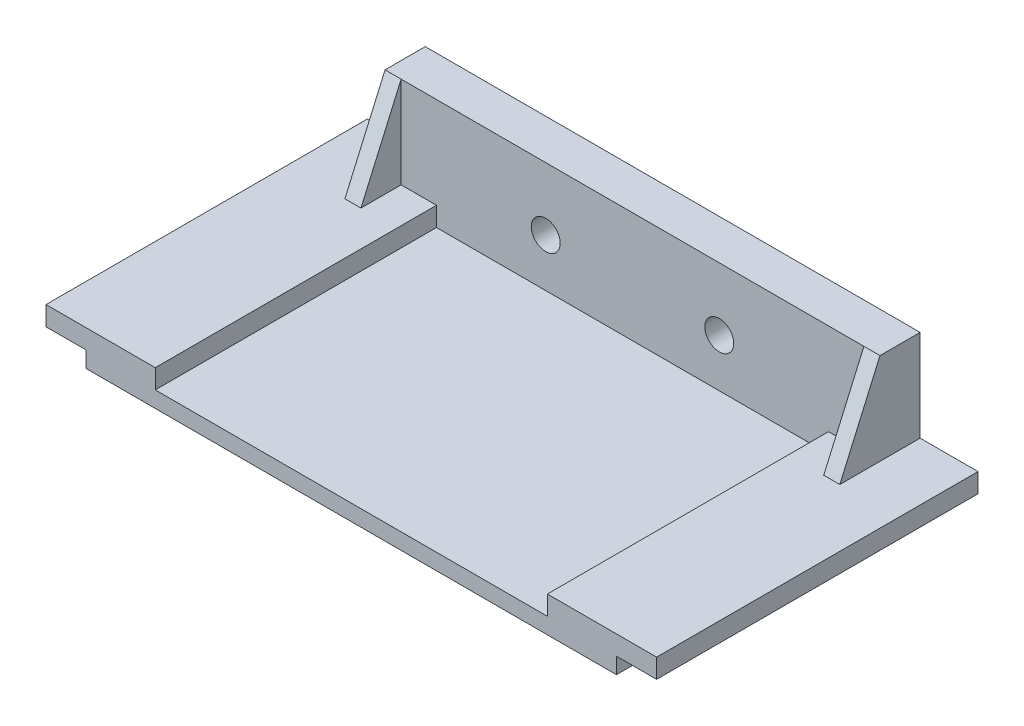
SolidWorks part; units mm, degrees
ref_plane "Front Plane" through (0, 0, 0) normal (0, 0, 1) x (1, 0, 0)
ref_plane "Top Plane" through (0, 0, 0) normal (0, 1, 0) x (1, 0, 0)
ref_plane "Right Plane" through (0, 0, 0) normal (1, 0, 0) x (0, 0, -1)
sketch "Sketch1" plane through (0, 0, 0) normal (0, 1, 0) x (1, 0, 0)
  line L1 (-48.26, -25.4) -> (48.26, -25.4)
  line L2 (-48.26, -25.4) -> (-48.26, 25.4)
  line L3 (-48.26, 25.4) -> (48.26, 25.4)
  line L4 (48.26, -25.4) -> (48.26, 25.4)
  line L5 (-48.26, -25.4) -> (48.26, 25.4) construction
  line L6 (-48.26, 25.4) -> (48.26, -25.4) construction
  point P0 (0, 0)
  dimension "D1" = 50.8
  dimension "D2" = 96.52
extrude "Boss-Extrude1" add sketch "Sketch1" along normal blind 5.588
sketch "Sketch2" plane through (0, 5.588, 0) normal (0, 1, 0) x (1, 0, 0)
  line L0 (48.26, 25.4) -> (-48.26, 25.4) construction
  line L1 (-30.988, -25.4) -> (30.988, -25.4)
  line L2 (-30.988, -25.4) -> (-30.988, 25.4)
  line L3 (-30.988, 25.4) -> (30.988, 25.4)
  line L4 (30.988, -25.4) -> (30.988, 25.4)
  line L5 (-30.988, -25.4) -> (30.988, 25.4) construction
  line L6 (-30.988, 25.4) -> (30.988, -25.4) construction
  point P0 (0, 0)
  line M6 (48.26, 25.4) -> (-48.26, 25.4)
  line M8 (-48.26, -25.4) -> (48.26, -25.4)
  dimension "D1" = 61.976
extrude "Cut-Extrude2" cut sketch "Sketch2" against normal blind 3.048 contours L4 L2 M8 M6 region at (0, 5.588, 0)
sketch "Sketch3" plane through (0, 0, 0) normal (0, -1, 0) x (-1, 0, 0)
  line L0 (48.26, -25.4) -> (-48.26, -25.4) construction
  line L1 (-48.26, 25.4) -> (-41.91, 25.4)
  line L2 (-48.26, 25.4) -> (-48.26, -25.4)
  line L3 (-48.26, -25.4) -> (-41.91, -25.4)
  line L4 (-41.91, 25.4) -> (-41.91, -25.4)
  line L6 (48.26, 25.4) -> (41.91, 25.4)
  line L7 (48.26, 25.4) -> (48.26, -25.4)
  line L8 (48.26, -25.4) -> (41.91, -25.4)
  line L9 (41.91, 25.4) -> (41.91, -25.4)
  dimension "D1" = 6.35
extrude "Cut-Extrude3" cut sketch "Sketch3" against normal blind 2.54
sketch "Sketch4" plane through (0, 2.54, 0) normal (0, 1, 0) x (1, 0, 0)
  line L0 (0, 0) -> (0, 50000) construction
  line L1 (30.988, 25.4) -> (-30.988, 25.4) construction
  line L2 (-39.116, 19.05) -> (39.116, 19.05)
  line L3 (-39.116, 19.05) -> (-39.116, 25.4)
  line L4 (-39.116, 25.4) -> (39.116, 25.4)
  line L5 (39.116, 19.05) -> (39.116, 25.4)
  line L6 (-39.116, 19.05) -> (39.116, 25.4) construction
  line L7 (-39.116, 25.4) -> (39.116, 19.05) construction
  point P3 (0, 22.225)
  dimension "D1" = 78.232
  dimension "D2" = 6.35
extrude "Boss-Extrude2" add sketch "Sketch4" along normal blind 17.526
sketch "Sketch5" plane through (0, 0, -25.4) normal (0, 0, -1) x (-1, 0, 0)
  line L0 (13.716, 10.16) -> (-13.716, 10.16) construction
  line L1 (39.116, 20.066) -> (39.116, 5.588) construction
  line L2 (-39.116, 20.066) -> (-39.116, 5.588) construction
  line L3 (-39.116, 20.066) -> (39.116, 20.066) construction
  circle A0 centre (13.716, 10.16) radius 2.286
  circle A1 centre (-13.716, 10.16) radius 2.286
  dimension "D1" = 4.572
  dimension "D2" = 25.4
  dimension "D3" = 25.4
  dimension "D4" = 9.906
extrude "Cut-Extrude4" cut sketch "Sketch5" against normal through all
sketch "Sketch6" plane through (-39.116, 0, 0) normal (-1, 0, 0) x (0, 0, 1)
  line L0 (-19.05, 5.588) -> (-12.7, 5.588)
  line L1 (-12.7, 5.588) -> (-19.05, 20.066)
  line L6 (-25.4, 20.066) -> (-25.4, 5.588)
  line L7 (-25.4, 5.588) -> (-19.05, 5.588)
  line L8 (-19.05, 5.588) -> (-19.05, 20.066)
  line L9 (-19.05, 20.066) -> (-25.4, 20.066)
  line L12 (-19.05, 5.588) -> (-19.05, 20.066)
  dimension "D1" = 6.35
  dimension "D2" = 0
extrude "Boss-Extrude3" add sketch "Sketch6" against normal blind 2.54
sketch "Sketch7" plane through (39.116, 0, 0) normal (1, 0, 0) x (0, 0, -1)
  line L3 (19.05, 5.588) -> (19.05, 20.066)
  line L4 (19.05, 20.066) -> (12.7, 5.588)
  line L5 (12.7, 5.588) -> (19.05, 5.588)
  line L6 (19.05, 5.588) -> (19.05, 20.066)
  line L7 (19.05, 20.066) -> (12.7, 5.588)
  line L8 (12.7, 5.588) -> (19.05, 5.588)
  dimension "D1" = 0
extrude "Boss-Extrude4" add sketch "Sketch7" against normal blind 2.54
sketch "Sketch8" plane through (0, 5.588, 0) normal (0, 1, 0) x (1, 0, 0)
  line L1 (48.26, 25.4) -> (41.91, 25.4)
  line L2 (48.26, 25.4) -> (48.26, 16.51)
  line L3 (48.26, 16.51) -> (41.91, 16.51)
  line L4 (41.91, 25.4) -> (41.91, 16.51)
  line L5 (-48.26, 25.4) -> (-41.91, 25.4)
  line L6 (-48.26, 25.4) -> (-48.26, 16.51)
  line L7 (-48.26, 16.51) -> (-41.91, 16.51)
  line L8 (-41.91, 25.4) -> (-41.91, 16.51)
  line L10 (-36.576, 19.05) -> (-30.988, 19.05) construction
  dimension "D1" = 2.54
extrude "Cut-Extrude5" cut sketch "Sketch8" against normal through all
sketch "Sketch9" plane through (0, 0, -16.51) normal (0, 0, -1) x (-1, 0, 0)
  line L0 (-48.26, 2.54) -> (-41.91, 2.54) construction
  line L1 (-41.91, 2.54) -> (-41.91, 5.588) construction
  line L2 (-41.91, 5.588) -> (-48.26, 5.588) construction
  line L3 (-48.26, 5.588) -> (-48.26, 2.54) construction
  line L4 (48.26, 2.54) -> (48.26, 5.588) construction
  line L5 (48.26, 5.588) -> (41.91, 5.588) construction
  line L6 (41.91, 5.588) -> (41.91, 2.54) construction
  line L7 (41.91, 2.54) -> (48.26, 2.54) construction
  line L8 (-48.26, 2.54) -> (-41.91, 2.54)
  line L9 (-41.91, 2.54) -> (-41.91, 5.588)
  line L10 (-41.91, 5.588) -> (-48.26, 5.588)
  line L11 (-48.26, 5.588) -> (-48.26, 2.54)
  line L12 (48.26, 2.54) -> (48.26, 5.588)
  line L13 (48.26, 5.588) -> (41.91, 5.588)
  line L14 (41.91, 5.588) -> (41.91, 2.54)
  line L15 (41.91, 2.54) -> (48.26, 2.54)
extrude "Boss-Extrude5" add sketch "Sketch9" along normal up to surface (8.89 mm away)
